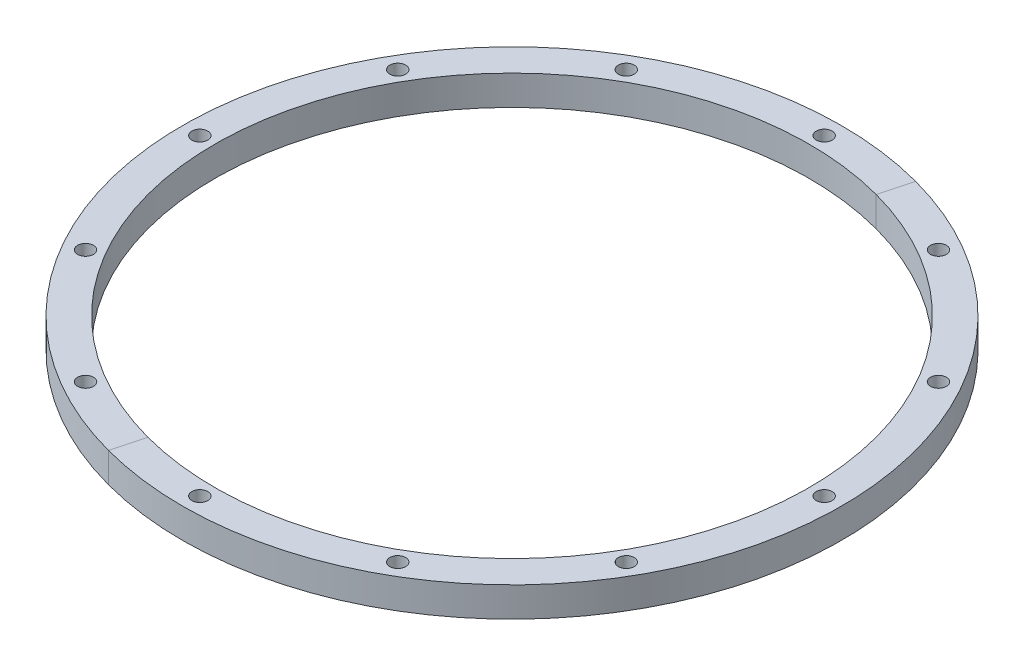
SolidWorks part; units mm, degrees
material "Hexcel AS4C (3000 Filaments)"
ref_plane "Front Plane" through (0, 0, 0) normal (0, 0, 1) x (1, 0, 0)
ref_plane "Top Plane" through (0, 0, 0) normal (0, 1, 0) x (1, 0, 0)
ref_plane "Right Plane" through (0, 0, 0) normal (1, 0, 0) x (0, 0, -1)
sketch "Sketch1" plane through (0, 0, 0) normal (0, 0, 1) x (1, 0, 0)
  line L0 (-60, 6.785) -> (-60, 0.785) construction
  line L1 (-66.5, 6.785) -> (-66.5, 0.785) construction
  line L2 (-60, 6.785) -> (-60, 0.785)
  line L3 (-66.5, 6.785) -> (-66.5, 0.785)
  line L4 (-60, 6.785) -> (-66.5, 6.785)
  line L5 (-60, 0.785) -> (-66.5, 0.785)
  line L6 (0, -200069.0475) -> (0, 200086.9028) construction
  line L7 (0, -200069.0475) -> (0, 200086.9028) construction
revolve "Revolve1" add sketch "Sketch1" angle 360 about L7
sketch "Sketch2" plane through (0, 6.785, 0) normal (0, 1, 0) x (1, 0, 0)
  circle A1 centre (0, 63) radius 1.6
  circle A2 centre (0, 63) radius 1.6
  dimension "D1" = 0
extrude "Cut-Extrude1" cut sketch "Sketch2" against normal through all
pattern_circular "CirPattern1" count 12 over 360 about axis through (0, -200069.0475, 0) along (0, -1, 0) of "Cut-Extrude1" reverse direction yes
ref_axis "CentralAxis" through (0, 7.085, 0) along (0, -1, 0)
ref_plane "Plane1" through (0, 0, 0) normal (0.9659, 0, 0.2588) x (0, -1, 0)
split "Split1" trim tools "Plane1" bodies to split 103 resulting bodies 104 105
